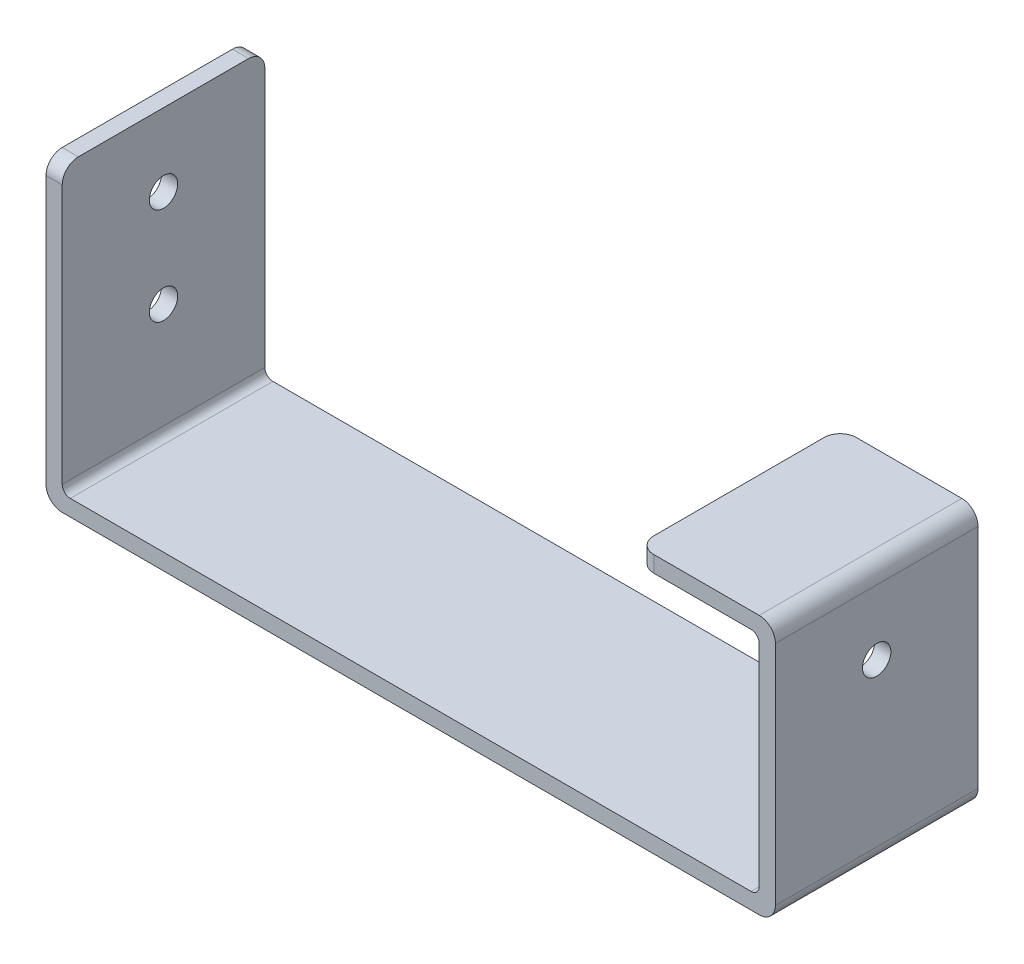
SolidWorks part; units mm, degrees
ref_plane "Plan de face" through (0, 0, 0) normal (0, 0, 1) x (1, 0, 0)
ref_plane "Plan de dessus" through (0, 0, 0) normal (0, 1, 0) x (1, 0, 0)
ref_plane "Plan de droite" through (0, 0, 0) normal (1, 0, 0) x (0, 0, -1)
sketch "Esquisse1" plane through (0, 0, 0) normal (0, 0, 1) x (1, 0, 0)
  line L0 (0, 0) -> (86, 0)
  line L1 (0, 0) -> (0, 35)
  line L2 (86, 0) -> (86, 28)
  line L3 (86, 28) -> (71, 28)
  dimension "D1" = 86
  dimension "D2" = 28
  dimension "D3" = 35
  dimension "D4" = 15
extrude "Extru.-Mince1" add sketch "Esquisse1" along normal blind 25 thin thin type one direction wall 2
fillet "Congé1" radius 1 1 edges at (0, 0, 12.5)
fillet "Congé2" radius 1 1 edges at (86, 0, 12.5)
fillet "Congé3" radius 2 1 edges at (88, -2, 12.5)
fillet "Congé4" radius 2 1 edges at (-2, -2, 12.5)
sketch "Esquisse2" plane through (-2, 0, 0) normal (-1, 0, 0) x (0, 0, 1)
  line L0 (-4.3852, 20) -> (27.735, 20) construction
  line L1 (12.5, 41.2385) -> (12.5, 10.4299) construction
  line L2 (0, 35) -> (0, 0) construction
  line L3 (25, 35) -> (0, 35) construction
  circle A0 centre (12.5, 26) radius 1.75
  circle A1 centre (12.5, 14) radius 1.75
  dimension "D7" = 3.5
  dimension "D10" = 3.5
  dimension "D1" = 12.5
  dimension "D2" = 15
  dimension "D3" = 6
  dimension "D4" = 6
extrude "Enlèv. mat.-Extru.1" cut sketch "Esquisse2" against normal blind 2
sketch "Esquisse3" plane through (88, 0, 0) normal (1, 0, 0) x (0, 0, -1)
  line L1 (-25, 0) -> (-25, 30) construction
  line L2 (-25, 30) -> (0, 30) construction
  circle A0 centre (-12.5, 20) radius 1.75
  dimension "D1" = 3.5
  dimension "D2" = 10
  dimension "D3" = 12.5
extrude "Enlèv. mat.-Extru.2" cut sketch "Esquisse3" against normal blind 2
fillet "Congé11" radius 2 1 edges at (88, 30, 12.5)
fillet "Congé12" radius 2 1 edges at (71, 29, 0)
fillet "Congé13" radius 2 1 edges at (71, 29, 25)
fillet "Congé14" radius 1 1 edges at (86, 28, 12.5)
fillet "Congé15" radius 2 1 edges at (-1, 35, 0)
fillet "Congé16" radius 2 1 edges at (-1, 35, 25)
